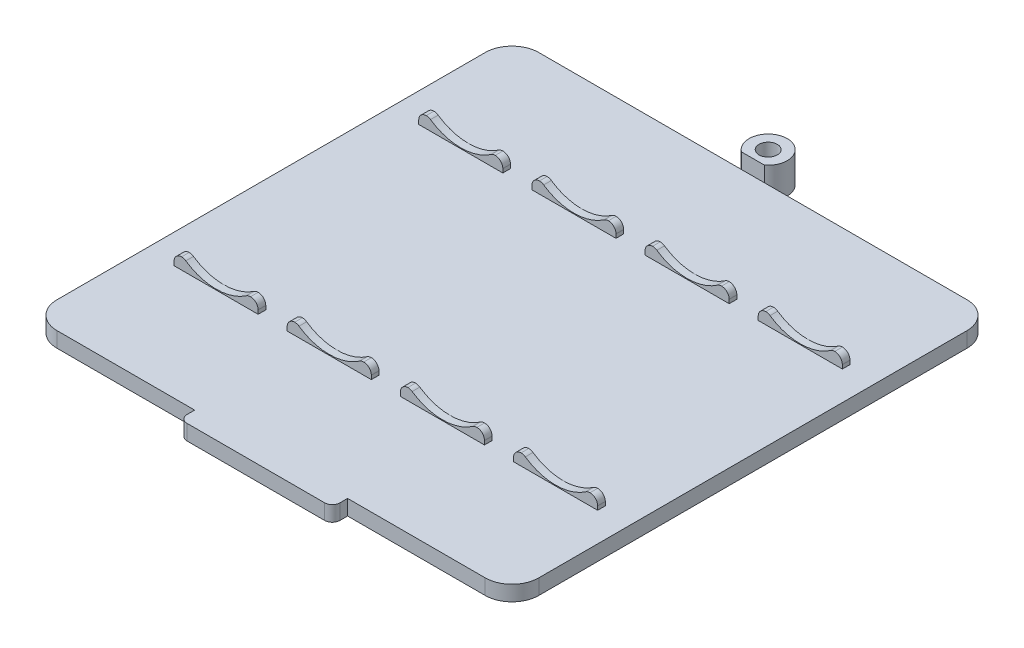
SolidWorks part; units mm, degrees
material "ABS PC"
ref_plane "Front Plane" through (0, 0, 0) normal (0, 0, 1) x (1, 0, 0)
ref_plane "Top Plane" through (0, 0, 0) normal (0, 1, 0) x (1, 0, 0)
ref_plane "Right Plane" through (0, 0, 0) normal (1, 0, 0) x (0, 0, -1)
sketch "Sketch1" plane through (0, 0, 0) normal (0, 1, 0) x (1, 0, 0)
  line L0 (10, -31.5) -> (28, -31.5)
  line L1 (-28, -31.5) -> (-10, -31.5)
  line L2 (-31.5, -28) -> (-31.5, 28)
  line L3 (-28, 31.5) -> (28, 31.5)
  line L4 (31.5, -28) -> (31.5, 28)
  line L5 (-31.5, -31.5) -> (31.5, 31.5) construction
  line L6 (-31.5, 31.5) -> (31.5, -31.5) construction
  line L8 (-10, -31.5) -> (-10, -32.5)
  line L9 (-9, -33.5) -> (9, -33.5)
  line L10 (10, -31.5) -> (10, -32.5)
  arc A0 (28, -31.5) -> (31.5, -28) centre (28, -28) ccw
  arc A1 (-28, -31.5) -> (-31.5, -28) centre (-28, -28) cw
  arc A2 (-31.5, 28) -> (-28, 31.5) centre (-28, 28) cw
  arc A3 (28, 31.5) -> (31.5, 28) centre (28, 28) cw
  arc A4 (9, -33.5) -> (10, -32.5) centre (9, -32.5) ccw
  arc A5 (-10, -32.5) -> (-9, -33.5) centre (-9, -32.5) ccw
  point P0 (0, 0)
  point P22 (0, -33.5)
  point P25 (10, -33.5)
  point P28 (-10, -33.5)
  dimension "D2" = 3.5
  dimension "D5" = 1
  dimension "D1" = 63
  dimension "D3" = 2
  dimension "D4" = 20
extrude "Boss-Extrude1" add sketch "Sketch1" along normal blind 2
sketch "Sketch2" plane through (0, 0, 0) normal (0, 1, 0) x (1, 0, 0)
  line L0 (28, 31.5) -> (-28, 31.5) construction
  circle A0 centre (0, 33.5) radius 2.5
  dimension "D1" = 5
  dimension "D2" = 2
extrude "Boss-Extrude3" add sketch "Sketch2" along normal blind 4
sketch "Sketch5" plane through (0, 2, 0) normal (0, 1, 0) x (1, 0, 0)
  line L0 (-27.7, 16) -> (-16.7, 16)
  line L1 (-27.7, -16) -> (-16.7, -16)
  line L2 (-22.2, 16) -> (-22.2, -16) construction
  line L3 (-31.5, 28) -> (-31.5, -28) construction
  line L4 (-12.9, -16) -> (-1.9, -16)
  line L5 (-12.9, 16) -> (-1.9, 16)
  line L6 (1.9, -16) -> (12.9, -16)
  line L7 (1.9, 16) -> (12.9, 16)
  line L8 (16.7, -16) -> (27.7, -16)
  line L9 (16.7, 16) -> (27.7, 16)
  point P7 (-22.2, 0)
  dimension "D1" = 11
  dimension "D2" = 32
  dimension "D3" = 3.8
  dimension "D5" = 3.8
  dimension "D4" = 4
extrude "Extrude-Thin2" add sketch "Sketch5" along normal blind 1.5 thin thin type mid plane wall 1
sketch "Sketch7" plane through (0, 0, 0) normal (0, 0, 1) x (1, 0, 0)
  line L0 (-27.7, 3.5) -> (-16.7, 3.5) construction
  line L1 (-28, 2) -> (-10, 2) construction
  circle A0 centre (-22.2, 9.1) radius 7
  circle A1 centre (-7.4, 9.1) radius 7
  circle A2 centre (7.4, 9.1) radius 7
  circle A3 centre (22.2, 9.1) radius 7
  point P6 (-22.2, 3.5)
  point P8 (-22.2, 2.1)
  dimension "D1" = 0.1
  dimension "D2" = 14
  dimension "D4" = 14.8
  dimension "D3" = 4
extrude "Cut-Extrude2" cut sketch "Sketch7" against normal through all both and the other way through all
fillet "Fillet2" radius 1 32 edges at (-16.7, 3.5, 16) (-18, 3.5, 16) (-26.4, 3.5, 16) (-27.7, 3.5, 16) (-11.6, 3.5, 16) (-12.9, 3.5, 16) (-1.9, 3.5, 16) (-3.2, 3.5, 16) (3.2, 3.5, 16) (1.9, 3.5, 16) (12.9, 3.5, 16) (11.6, 3.5, 16) (16.7, 3.5, 16) (18, 3.5, 16) (26.4, 3.5, 16) (27.7, 3.5, 16) (18, 3.5, -16) (16.7, 3.5, -16) (27.7, 3.5, -16) (26.4, 3.5, -16) (12.9, 3.5, -16) (11.6, 3.5, -16) (3.2, 3.5, -16) (1.9, 3.5, -16) (-1.9, 3.5, -16) (-3.2, 3.5, -16) (-11.6, 3.5, -16) (-12.9, 3.5, -16) (-16.7, 3.5, -16) (-18, 3.5, -16) (-26.4, 3.5, -16) (-27.7, 3.5, -16)
sketch "Sketch8" plane through (0, 4, 0) normal (0, 1, 0) x (1, 0, 0)
  line L0 (-1.5, 31.5) -> (1.5, 31.5)
  circle A0 centre (0, 33.5) radius 2.5 construction
  arc A1 (-1.5, 31.5) -> (1.5, 31.5) centre (0, 33.5) ccw
extrude "Cut-Extrude3" cut sketch "Sketch8" against normal up to surface (2 mm away) up to face at (0, 2, 8.3071)
hole_wizard "CBORE for M2 Hex Head Bolt2" positions "Sketch13" profile "Sketch14" counterbore size "M5" standard "ISO" end condition through all
sketch "Sketch13" plane through (0, 0, 0) normal (0, -1, 0) x (-1, 0, 0)
  point P0 (0, 33.5)
sketch "Sketch14" plane through (0, 0, -33.5) normal (1, 0, 0) x (0, 0, -1)
  line L0 (0, 0) -> (0, 4)
  line L1 (0, 4) -> (1.2, 4)
  line L3 (1.2, 4) -> (1.2, 1.76)
  line L4 (1.2, 1.76) -> (2.2, 1.76)
  line L5 (2.2, 1.76) -> (2.2, 0)
  line L7 (2.2, 0) -> (0, 0)
  line L11 (0, -6.35) -> (0, 107.95) construction
  dimension "Thru Hole Dia." = 2.4
  dimension "Thru Hole Depth" = 4
  dimension "C'Bore Dia." = 4.4
  dimension "C'Bore Depth" = 1.76
